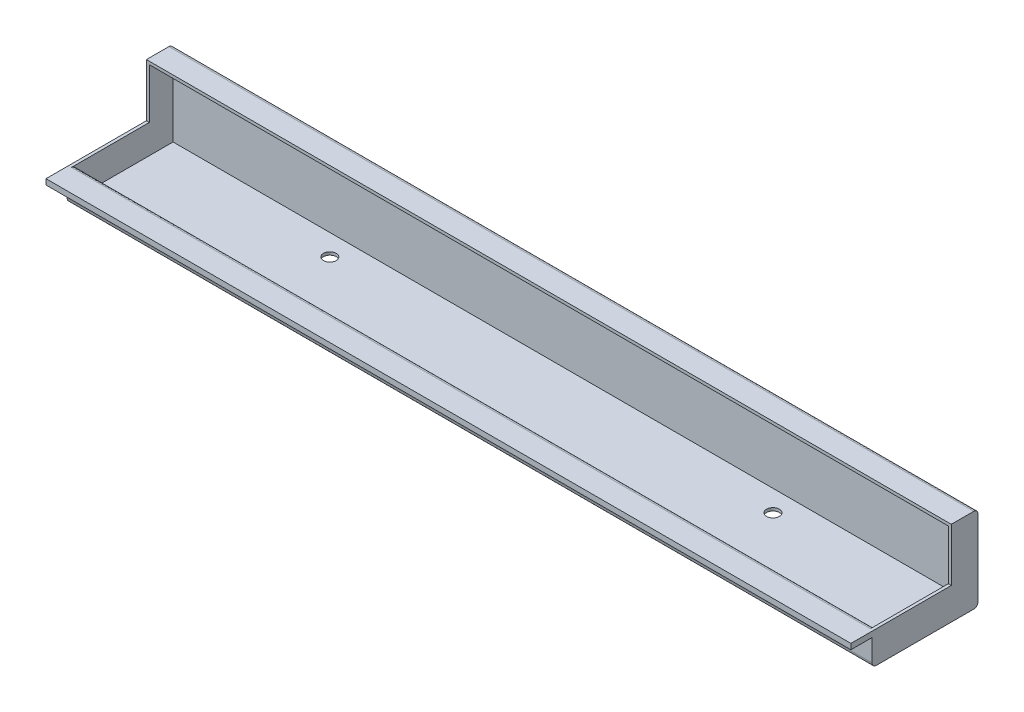
SolidWorks part; units mm, degrees
ref_plane "Front Plane" through (0, 0, 0) normal (0, 0, 1) x (1, 0, 0)
ref_plane "Top Plane" through (0, 0, 0) normal (0, 1, 0) x (1, 0, 0)
ref_plane "Right Plane" through (0, 0, 0) normal (1, 0, 0) x (0, 0, -1)
sketch "Sketch1" plane through (0, 0, 0) normal (0, 0, 1) x (1, 0, 0)
  line L1 (-241.3, -25.4) -> (241.3, -25.4)
  line L2 (-241.3, -25.4) -> (-241.3, 25.4)
  line L3 (-241.3, 25.4) -> (241.3, 25.4)
  line L4 (241.3, -25.4) -> (241.3, 25.4)
  line L5 (-241.3, -25.4) -> (241.3, 25.4) construction
  line L6 (-241.3, 25.4) -> (241.3, -25.4) construction
  point P0 (0, 0)
  dimension "D1" = 482.6
  dimension "D2" = 50.8
extrude "Boss-Extrude1" add sketch "Sketch1" along normal blind 76.2
sketch "Sketch2" plane through (0, 25.4, 0) normal (0, 1, 0) x (1, 0, 0)
  line L0 (241.3, -76.2) -> (241.3, 0) construction
  line L1 (-241.3, 0) -> (241.3, 0)
  line L2 (-241.3, 0) -> (-241.3, -16.002)
  line L3 (-241.3, -16.002) -> (241.3, -16.002)
  line L4 (241.3, 0) -> (241.3, -16.002)
  line L5 (-241.3, -38.1) -> (-219.8341, -38.1)
  line L6 (-241.3, -76.2) -> (-241.3, 0) construction
  line L7 (241.3, -76.2) -> (241.3, -60.198)
  line L8 (-241.3, -76.2) -> (-241.3, -60.198)
  line L9 (-241.3, -76.2) -> (241.3, -76.2)
  line L10 (-241.3, -60.198) -> (241.3, -60.198)
  line M6 (-241.3, 0) -> (-241.3, -76.2)
  line M8 (241.3, -76.2) -> (241.3, 0)
  dimension "D1" = 16.002
extrude "Cut-Extrude2" cut sketch "Sketch2" against normal blind 49.022 contours L10 L3 M6 M8 region at (0, 25.4, 38.1)
sketch "Sketch3" plane through (0, 25.4, 0) normal (0, 1, 0) x (1, 0, 0)
  line L1 (-241.3, -60.198) -> (241.3, -60.198)
  line L2 (-241.3, -60.198) -> (-241.3, -76.2)
  line L3 (-241.3, -76.2) -> (241.3, -76.2)
  line L4 (241.3, -60.198) -> (241.3, -76.2)
extrude "Cut-Extrude3" cut sketch "Sketch3" against normal blind 31.75
sketch "Sketch4" plane through (0, 0, 76.2) normal (0, 0, 1) x (1, 0, 0)
  line L0 (241.3, -25.4) -> (241.3, -6.35) construction
  line L1 (-241.3, -25.4) -> (241.3, -25.4)
  line L2 (-241.3, -25.4) -> (-241.3, -9.652)
  line L3 (-241.3, -9.652) -> (241.3, -9.652)
  line L4 (241.3, -25.4) -> (241.3, -9.652)
  line L5 (-241.3, -6.35) -> (241.3, -6.35) construction
  dimension "D1" = 3.302
extrude "Cut-Extrude4" cut sketch "Sketch4" against normal blind 12.7
shell "Shell2" thickness 1.778 removed face at (0, 0.889, 16.002)
sketch "Sketch5" plane through (0, 0, 60.198) normal (0, 0, -1) x (-1, 0, 0)
  line L0 (-241.3, -6.35) -> (241.3, -6.35) construction
  line L1 (241.3, -23.622) -> (239.522, -23.622)
  line L2 (241.3, -23.622) -> (241.3, -6.35)
  line L3 (241.3, -6.35) -> (239.522, -6.35)
  line L4 (239.522, -23.622) -> (239.522, -6.35)
  line L5 (0, -23.622) -> (0, -9.0933)
  line L6 (241.3, -23.622) -> (-241.3, -23.622) construction
  line L7 (-239.522, -23.622) -> (-239.522, -6.35)
  line L8 (-241.3, -6.35) -> (-239.522, -6.35)
  line L9 (-241.3, -23.622) -> (-241.3, -6.35)
  line L10 (-241.3, -23.622) -> (-239.522, -23.622)
  line M2 (241.3, -6.35) -> (-241.3, -6.35)
  line M4 (-241.3, -23.622) -> (241.3, -23.622)
  line M5 (241.3, -23.622) -> (241.3, -6.35)
  dimension "D1" = 1.778
extrude "Boss-Extrude2" add sketch "Sketch5" along normal blind 44.45 contours L4 M4 M5 M2 | L7 L8 L9 L10 region at (-240.411, -14.986, 60.198)
fillet "Fillet1" radius 2.54 4 edges at (0, -6.35, 60.198) (0, -25.4, 63.5) (0, -25.4, 0) (0, 25.4, 0)
sketch "Sketch6" plane through (0, -23.622, 0) normal (0, 1, 0) x (1, 0, 0)
  line L0 (-239.522, -1.778) -> (-239.522, -14.478)
  line L1 (-239.522, -60.198) -> (-239.522, -1.778) construction
  line L2 (-239.522, -14.478) -> (-132.842, -14.478)
  line L3 (0, -1.778) -> (0, -14.478)
  line L4 (-239.522, -1.778) -> (239.522, -1.778) construction
  circle A0 centre (-132.842, -14.478) radius 3.81
  circle A1 centre (132.842, -14.478) radius 3.81
  dimension "D1" = 12.7
  dimension "D2" = 106.68
extrude "Cut-Extrude5" cut sketch "Sketch6" against normal blind 44.45 contours A0 | A1 region at (-132.842, -23.622, 18.1802)
